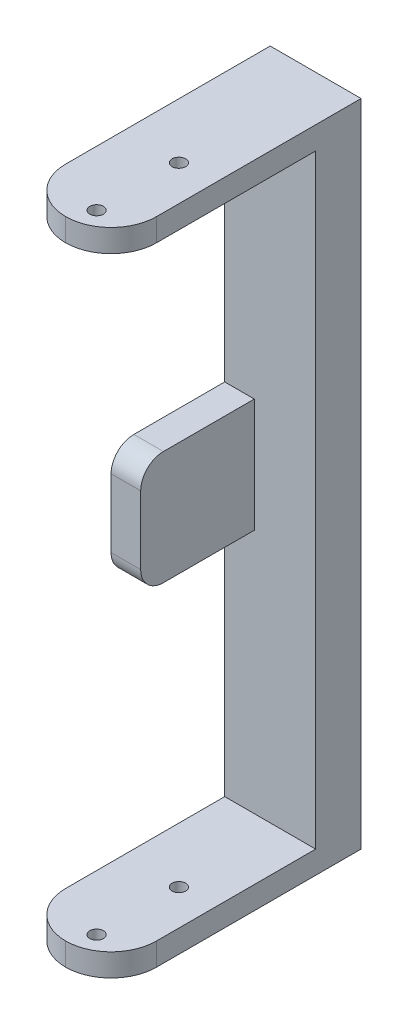
SolidWorks part; units mm, degrees
ref_plane "Front Plane" through (0, 0, 0) normal (0, 0, 1) x (1, 0, 0)
ref_plane "Top Plane" through (0, 0, 0) normal (0, 1, 0) x (1, 0, 0)
ref_plane "Right Plane" through (0, 0, 0) normal (1, 0, 0) x (0, 0, -1)
sketch "Sketch1" plane through (0, 0, 0) normal (0, 0, 1) x (1, 0, 0)
  line L0 (-20, 71.5) -> (0, 71.5)
  line L1 (-20, 71.5) -> (-20, -71.5)
  line L2 (-20, -71.5) -> (0, -71.5)
  line L3 (0, 71.5) -> (0, -71.5)
  point P5 (0, 0)
  dimension "D1" = 20
  dimension "D2" = 143
extrude "Boss-Extrude1" add sketch "Sketch1" along normal blind 10
sketch "Sketch2" plane through (0, 0, 10) normal (0, 0, 1) x (1, 0, 0)
  line L0 (0, 71.5) -> (-20, 71.5) construction
  line L1 (-20, 71.5) -> (0, 71.5)
  line L2 (-20, 71.5) -> (-20, 66.5)
  line L3 (-20, 66.5) -> (0, 66.5)
  line L4 (0, 71.5) -> (0, 66.5)
  line L5 (0, -71.5) -> (0, 71.5) construction
  line L6 (-20, 71.5) -> (-20, -71.5) construction
  line L7 (-38.3047, 0) -> (23.706, 0) construction
  line L8 (0, -71.5) -> (0, -66.5)
  line L9 (-20, -66.5) -> (0, -66.5)
  line L10 (-20, -71.5) -> (-20, -66.5)
  line L11 (-20, -71.5) -> (0, -71.5)
  line L13 (-13.49, 12.5) -> (-20, 12.5)
  line L14 (-13.49, 12.5) -> (-13.49, -12.5)
  line L15 (-13.49, -12.5) -> (-20, -12.5)
  line L16 (-20, 12.5) -> (-20, -12.5)
  point P20 (-20, 0)
  line M8 (-20, 71.5) -> (-20, -71.5)
  line M9 (-20, -71.5) -> (0, -71.5)
  line M10 (0, -71.5) -> (0, 71.5)
  line M11 (0, 71.5) -> (-20, 71.5)
  dimension "D1" = 5
  dimension "D2" = 25
  dimension "D3" = 6.51
  dimension "D4" = 25
  dimension "D5" = 6.51
  dimension "D6" = 0
extrude "Boss-Extrude2" add sketch "Sketch2" along normal blind 45 contours L3 M8 M10 M11 | L9 M8 M9 M10 region at (-10, 69, 10) region at (-10, -69, 10)
fillet "Fillet1" radius 10 4 edges at (0, -69, 55) (-20, -69, 55) (-20, 69, 55) (0, 69, 55)
sketch "Sketch6" plane through (0, 71.5, 0) normal (0, 1, 0) x (1, 0, 0)
  line L0 (-20, -44.9836) -> (-20, -19.1471)
  line L1 (-20, -19.1471) -> (0, -19.1471)
  line L2 (0, -19.1471) -> (0, -45)
  arc A0 (-20, -44.9836) -> (0, -45) centre (-10, -44.9918) ccw
  circle A1 centre (-7.8, -32.2836) radius 1.5
  circle A2 centre (-7.8, -50.3836) radius 1.5
  dimension "D3" = 3
  dimension "D4" = 3
  dimension "D5" = 10
  dimension "D1" = 20
  dimension "D2" = 25.8365
  dimension "D6" = 12.2
  dimension "D7" = 12.2
  dimension "D8" = 31.2365
  dimension "D9" = 13.1365
extrude "Cut-Extrude1" cut sketch "Sketch6" against normal through all contours A1 | A2 region at (-7.8, 71.5, 32.2836) region at (-7.8, 71.5, 50.3836)
extrude "Boss-Extrude3" add sketch "Sketch2<3>" along normal blind 25 contours L7 L16 L15 L14 | L7 L14 L13 M8 region at (-16.745, 6.25, 10) region at (-16.745, -6.25, 10)
sketch "Sketch2<3>" plane through (0, 0, 10) normal (0, 0, 1) x (1, 0, 0) same geometry as "Sketch2"
fillet "Fillet2" radius 5 2 edges at (-16.745, -12.5, 35) (-16.745, 12.5, 35)
